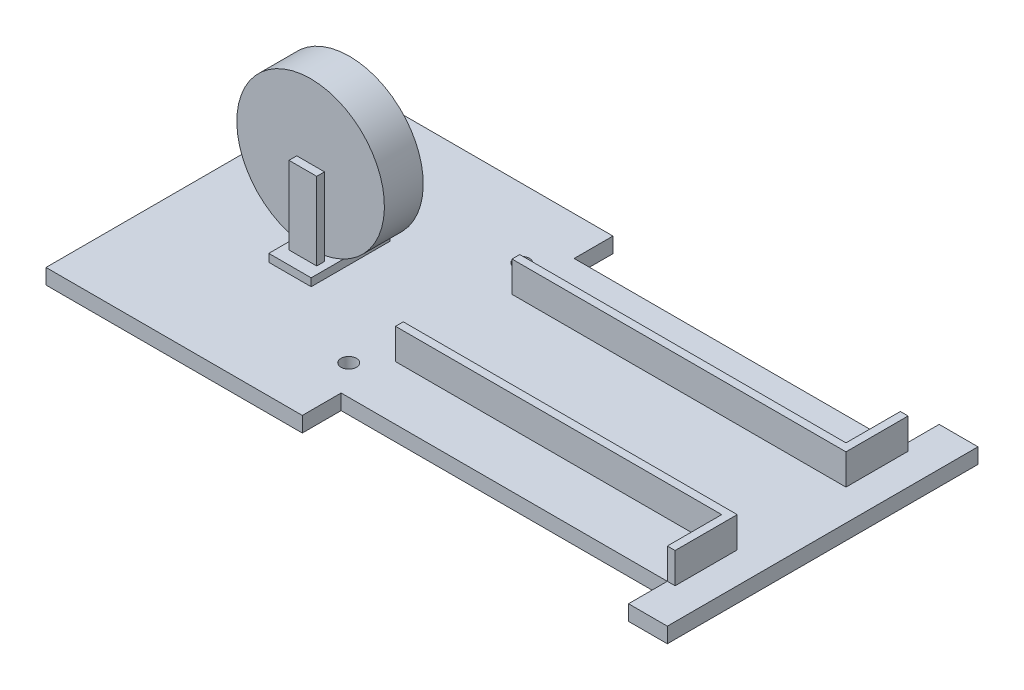
SolidWorks part; units mm, degrees
ref_plane "Front Plane" through (0, 0, 0) normal (0, 0, 1) x (1, 0, 0)
ref_plane "Top Plane" through (0, 0, 0) normal (0, 1, 0) x (1, 0, 0)
ref_plane "Right Plane" through (0, 0, 0) normal (1, 0, 0) x (0, 0, -1)
sketch "Sketch1" plane through (0, 0, 0) normal (0, 1, 0) x (1, 0, 0)
  line L0 (88.9, 50.8) -> (88.9, 38.1)
  line L1 (-101.6, 50.8) -> (101.6, 50.8)
  line L2 (-101.6, 50.8) -> (-101.6, -50.8)
  line L3 (-101.6, -50.8) -> (101.6, -50.8)
  line L4 (101.6, 50.8) -> (101.6, -50.8)
  line L5 (-101.6, 50.8) -> (101.6, -50.8) construction
  line L6 (-101.6, -50.8) -> (101.6, 50.8) construction
  line L7 (88.9, 38.1) -> (-17.78, 38.1)
  line L8 (-17.78, 38.1) -> (-17.78, 50.8)
  line L9 (-111.76, 0) -> (111.76, 0) construction
  line L10 (88.9, -50.8) -> (88.9, -38.1)
  line L11 (88.9, -38.1) -> (-17.78, -38.1)
  line L12 (-17.78, -38.1) -> (-17.78, -50.8)
  point P0 (0, 0)
  dimension "D1" = 203.2
  dimension "D2" = 101.6
  dimension "D3" = 12.7
  dimension "D4" = 106.68
  dimension "D5" = 12.7
extrude "Boss-Extrude1" add sketch "Sketch1" along normal blind 5 contours L12 L11 L10 L3 L4 L1 L0 L7 L8 L2 region at (-5.3724, 0, 0)
sketch "Sketch2" plane through (0, 5, 0) normal (0, 1, 0) x (1, 0, 0)
  line L0 (88.9, -38.1) -> (88.9, -20.32)
  line L1 (88.9, -20.32) -> (-17.78, -20.32)
  line L2 (-17.78, -20.32) -> (-17.78, -17.78)
  line L3 (-17.78, -17.78) -> (91.44, -17.78)
  line L4 (91.44, -17.78) -> (91.44, -38.1)
  line L5 (91.44, -38.1) -> (88.9, -38.1)
  line L6 (-111.76, 0) -> (111.76, 0) construction
  line L7 (91.44, 17.78) -> (91.44, 38.1)
  line L8 (-17.78, 17.78) -> (91.44, 17.78)
  line L9 (-17.78, 20.32) -> (-17.78, 17.78)
  line L10 (88.9, 20.32) -> (-17.78, 20.32)
  line L11 (88.9, 38.1) -> (88.9, 20.32)
  line L12 (91.44, 38.1) -> (88.9, 38.1)
  dimension "D1" = 17.78
  dimension "D2" = 2.54
  dimension "D3" = 2.54
extrude "Boss-Extrude2" add sketch "Sketch2" along normal blind 10
sketch "Sketch3" plane through (0, 5, 0) normal (0, 1, 0) x (1, 0, 0)
  line L0 (-111.76, 0) -> (111.76, 0) construction
  circle A0 centre (-25.0869, 28.3123) radius 2.54
  circle A1 centre (-25.0869, -28.3123) radius 2.54
  dimension "D1" = 5.08
extrude "Cut-Extrude1" cut sketch "Sketch3" against normal through all
sketch "Sketch5" plane through (0, 5, 0) normal (0, 1, 0) x (1, 0, 0)
  line L0 (-101.6, 50.8) -> (-17.78, -50.8) construction
  line L1 (-17.78, 50.8) -> (-101.6, -50.8) construction
  line L3 (-66.6159, 12.9213) -> (-52.7641, 12.9213)
  line L4 (-66.6159, 12.9213) -> (-66.6159, -12.9213)
  line L5 (-66.6159, -12.9213) -> (-52.7641, -12.9213)
  line L6 (-52.7641, 12.9213) -> (-52.7641, -12.9213)
  line L7 (-66.6159, 12.9213) -> (-52.7641, -12.9213) construction
  line L8 (-66.6159, -12.9213) -> (-52.7641, 12.9213) construction
  point P8 (-59.69, 0)
extrude "Boss-Extrude3" add sketch "Sketch5" along normal blind 2.54
sketch "Sketch6" plane through (0, 7.54, 0) normal (0, 1, 0) x (1, 0, 0)
  line L1 (-64.2702, 9.1113) -> (-55.1912, 9.1113)
  line L2 (-64.2702, 9.1113) -> (-64.2702, 6.5713)
  line L3 (-64.2702, 6.5713) -> (-55.1912, 6.5713)
  line L4 (-55.1912, 9.1113) -> (-55.1912, 6.5713)
  line L5 (-64.2702, 9.1113) -> (-55.1912, 6.5713) construction
  line L6 (-64.2702, 6.5713) -> (-55.1912, 9.1113) construction
  point P0 (-59.7307, 7.8413)
  dimension "D1" = 5.08
  dimension "D2" = 2.54
extrude "Boss-Extrude7" add sketch "Sketch6" along normal blind 25.4
sketch "Sketch9" plane through (0, 0, -6.5713) normal (0, 0, 1) x (1, 0, 0)
  line L0 (-64.2702, 32.94) -> (-55.1912, 32.94) construction
  circle A0 centre (-59.7307, 32.94) radius 24.13
  dimension "D1" = 48.26
extrude "Boss-Extrude10" add sketch "Sketch9" along normal blind 12.7
sketch "Sketch12" plane through (0, 0, 6.1287) normal (0, 0, 1) x (1, 0, 0)
  line L0 (-64.2702, 32.94) -> (-55.1912, 32.94)
  line L1 (-64.2702, 32.94) -> (-64.2702, 7.3288)
  line L2 (-55.1912, 32.94) -> (-55.1912, 7.3288)
  line L3 (-64.2702, 7.3288) -> (-55.1912, 7.3288)
  line L4 (-64.2702, 9.2409) -> (-64.2702, 7.54) construction
  line L5 (-55.1912, 9.2409) -> (-55.1912, 7.54) construction
extrude "Boss-Extrude11" add sketch "Sketch12" along normal blind 2.54
ref_plane "Plane1" through (-64.2702, 9.2409, -6.5713) normal (0.9821, -0.1881, 0) x (-0.1881, -0.9821, 0)
ref_plane "Plane2" through (-64.2702, 9.2409, 6.1287) normal (0.9821, -0.1881, 0) x (-0.1881, -0.9821, 0)
sketch "Sketch15" plane through (0, 5, 0) normal (0, 1, 0) x (1, 0, 0)
  line L0 (-17.78, 38.1) -> (-17.78, 20.32)
  line L1 (88.9, 38.1) -> (-17.78, 38.1) construction
  line L2 (-17.78, 20.32) -> (88.9, 20.32)
  line L3 (88.9, 20.32) -> (88.9, 38.1)
  line L4 (88.9, 38.1) -> (-17.78, 38.1)
  line L5 (-31.3885, 0) -> (31.3885, 0) construction
  line L6 (88.9, -20.32) -> (88.9, -38.1)
  line L7 (-17.78, -20.32) -> (88.9, -20.32)
  line L8 (-17.78, -38.1) -> (-17.78, -20.32)
  line L9 (88.9, -38.1) -> (-17.78, -38.1)
